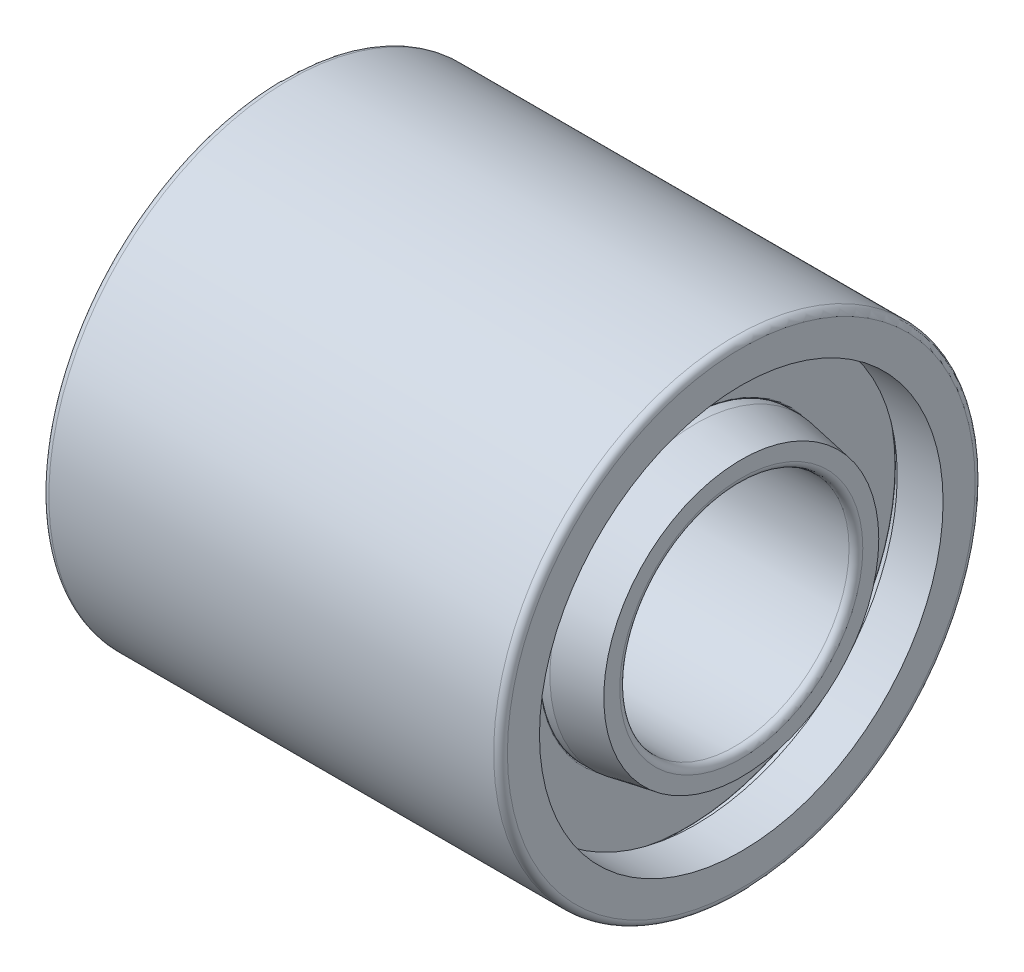
SolidWorks part; units mm, degrees
ref_plane "Plane1" through (0, 0, 0) normal (0, 0, 1) x (1, 0, 0)
ref_plane "Plane2" through (0, 0, 0) normal (0, 1, 0) x (1, 0, 0)
ref_plane "Plane3" through (0, 0, 0) normal (1, 0, 0) x (0, 0, -1)
sketch "Clipboard" plane through (0, 0, 0) normal (0, 0, 1) x (1, 0, 0)
  line L0 (-10, 0) -> (10, 0) construction
  line L1 (0, 0) -> (25.3745, -0.8861)
  line L2 (0, 0) -> (15.4906, 0.5409)
  line L3 (0, 0) -> (36.5877, -1.2777)
  line L4 (0, 0) -> (-22.3573, -0.3902)
  dimension "Race_OD" = 36.61
  dimension "Race_ID" = 25.39
sketch "OutRacSke" plane through (0, 0, 0) normal (0, 0, 1) x (1, 0, 0)
  line L0 (-16, 17.6038) -> (-20, 17.6038)
  line L1 (-20, 17.6038) -> (-20, 20.4)
  line L2 (-19.4, 21) -> (19.4, 21)
  line L3 (20, 20.4) -> (20, 17.6038)
  line L4 (20, 17.6038) -> (16, 17.6038)
  line L5 (16, 17.6038) -> (16, 18.305)
  line L6 (16, 18.305) -> (-16, 18.305)
  line L7 (-16, 18.305) -> (-16, 17.6038)
  line L8 (-90, 0) -> (90, 0) construction
  arc A0 (-20, 20.4) -> (-19.4, 21) centre (-19.4, 20.4) cw
  arc A1 (19.4, 21) -> (20, 20.4) centre (19.4, 20.4) cw
  dimension "Race_OD" = 36.61
  dimension "radius" = 0.6
  dimension "Width" = 40
  dimension "halfWidth" = 20
  dimension "groove_dp" = 0.7013
  dimension "Cyl_Len" = 32
revolve "OuterRace" add sketch "OutRacSke" angle 360 about L8 reverse direction yes
sketch "RolDetSke" plane through (0, 0, 0) normal (0, 0, 1) x (1, 0, 0)
  line L0 (-15.2, 18.1976) -> (-15.2, 15.5)
  line L1 (-15.2, 15.5) -> (15.2, 15.5)
  line L2 (15.2, 15.5) -> (15.2, 18.1976)
  line L3 (15.0876, 18.31) -> (-15.0876, 18.31)
  line L4 (-33.6, 15.5) -> (33.6, 15.5) construction
  arc A0 (15.2, 18.1976) -> (15.0876, 18.31) centre (15.0876, 18.1976) ccw
  arc A1 (-15.0876, 18.31) -> (-15.2, 18.1976) centre (-15.0876, 18.1976) ccw
  dimension "radius" = 0.1124
  dimension "Roller_diameter" = 5.62
  dimension "halfLength" = 15.2
revolve "RollerDetailed" [suppressed] add sketch "RolDetSke" angle 360 about L4 reverse direction yes
ref_axis "Axis1" through (-50, 0, 0) along (1, 0, 0)
sketch "RolSimSke" plane through (0, 101.6, 0) normal (0, 0, 1) x (1, 0, 0)
  line L0 (-15.2, -83.4024) -> (-15.2, -88.7976)
  line L1 (25.4, -101.6) -> (-25.4, -101.6) construction
  line L2 (15.2, -88.7976) -> (15.2, -83.4024)
  line L3 (15.0876, -83.29) -> (-15.0876, -83.29)
  line L5 (15.0876, -88.91) -> (-15.0876, -88.91)
  arc A0 (15.2, -83.4024) -> (15.0876, -83.29) centre (15.0876, -83.4024) ccw
  arc A1 (-15.0876, -83.29) -> (-15.2, -83.4024) centre (-15.0876, -83.4024) ccw
  arc A2 (15.2, -88.7976) -> (15.0876, -88.91) centre (15.0876, -88.7976) cw
  arc A3 (-15.0876, -88.91) -> (-15.2, -88.7976) centre (-15.0876, -88.7976) cw
  dimension "radius" = 0.1124
  dimension "D1" = 12.69
  dimension "Roller_diameter" = 5.62
  dimension "halfLength" = 15.2
revolve "RollersSimplified" add sketch "RolSimSke" angle 360 about L1
sketch "InsRacSke" plane through (0, 0, 0) normal (0, 0, 1) x (1, 0, 0)
  line L0 (-16, 12.695) -> (-20, 11.9938)
  line L1 (-20, 11.9938) -> (-20, 10.6)
  line L2 (-19.4, 10) -> (19.4, 10)
  line L3 (20, 10.6) -> (20, 11.9937)
  line L4 (20, 11.9937) -> (16, 12.695)
  line L5 (16, 12.695) -> (-16, 12.695)
  line L6 (-90, 0) -> (90, 0) construction
  line L7 (0, 0) -> (0, 177.8) construction
  arc A0 (-20, 10.6) -> (-19.4, 10) centre (-19.4, 10.6) ccw
  arc A1 (19.4, 10) -> (20, 10.6) centre (19.4, 10.6) ccw
  dimension "radius" = 0.6
  dimension "Race_ID" = 25.39
  dimension "Width" = 40
  dimension "halfWidth" = 20
  dimension "groove_dp" = 0.7013
  dimension "Cyl_Len" = 32
revolve "InnerRace" add sketch "InsRacSke" angle 360 about L6 reverse direction yes
pattern_circular "RollersDetailed" [suppressed] count 2 every 180 about axis through (-50, 0, 0) along (1, 0, 0)
sketch "CagSpiSke" plane through (0, 0, 0) normal (0, 0, 1) x (1, 0, 0)
  line L0 (18, 14.7975) -> (18, 16.2025)
  line L1 (18, 16.2025) -> (-18, 16.2025)
  line L2 (-18, 16.2025) -> (-18, 14.7975)
  line L3 (-18, 14.7975) -> (18, 14.7975)
  line L4 (-90, 0) -> (90, 0) construction
revolve "CageSpine" [suppressed] add sketch "CagSpiSke" angle 0.001 about L4
equation "\"CLdia@Clipboard\" =  ( \"Race_OD@Clipboard\" + \"Race_ID@Clipboard\" )  / 4"
equation "\"Race_OD@OutRacSke\" = \"Race_OD@Clipboard\""
equation "\"halfCylLen@OutRacSke\" = \"Cyl_Len@OutRacSke\" / 2"
equation "\"RolCLRad@RolDetSke\" = \"CLdia@Clipboard\""
equation "\"Roller_diameter@RolDetSke\" =  ( \"Race_OD@Clipboard\" - \"Race_ID@Clipboard\" )  / 2 + .01"
equation "\"Roller_diameter@RolSimSke\" =  ( \"Race_OD@Clipboard\" - \"Race_ID@Clipboard\" )  / 2 + .01"
equation "\"radius@RolDetSke\" = \"Roller_diameter@RolDetSke\" / 50"
equation "\"Length@RolDetSke\" = \"Cyl_Len@OutRacSke\" * .95"
equation "\"halfLength@RolDetSke\" = \"Length@RolDetSke\" / 2"
equation "\"thickness@CagSpiSke\"  = \"Roller_diameter@RolDetSke\" * .25"
equation "\"Cag_IR@CagSpiSke\" =  \"RolCLRad@RolDetSke\" * 2 - \"thickness@CagSpiSke\""
equation "\"Rol_Length@RolSimSke\" = \"Cyl_Len@InsRacSke\" * .95"
equation "\"halfLength@RolSimSke\" = \"Rol_Length@RolSimSke\" / 2"
equation "\"radius@RolSimSke\" = \"radius@RolDetSke\""
equation "\"D1@RolSimSke\" = \"CLdia@Clipboard\" -  ( \"Roller_diameter@RolSimSke\" / 2 ) "
equation "\"Max_count@Clipboard\" = int( 3.14159265 / atn(( \"Roller_diameter@RolDetSke\" / 2) / sqr( \"RolCLRad@RolDetSke\"  *  \"RolCLRad@RolDetSke\" - ( \"Roller_diameter@RolDetSke\" / 2) *  ( \"Roller_diameter@RolDetSke\" / 2))))"
equation "\"Max_count@Clipboard\" = ((sgn( \"Max_count@Clipboard\" - \"Count@Clipboard\" )-1)*( \"Max_count@Clipboard\" - \"Count@Clipboard\" ))/-2+ \"Count@Clipboard\""
equation "\"Count@RollersDetailed\" = int( \"Show_count@Clipboard\" ) "
equation "\"Count@RollersDetailed\" = ((sgn( \"Count@RollersDetailed\" - \"Max_count@Clipboard\" )-1)*( \"Count@RollersDetailed\" - \"Max_count@Clipboard\" ))/-2+ \"Max_count@Clipboard\""
equation "\"Count@RollersDetailed\" = ((sgn( \"Count@RollersDetailed\" - \"Min_count@Clipboard\" )+1)*( \"Count@RollersDetailed\" - \"Min_count@Clipboard\"))/2 +\"Min_count@Clipboard\""
equation "\"Angle@RollersDetailed\" = 360.0 / \"Max_count@Clipboard\""
equation "\"radius@InsRacSke\" = \"radius@OutRacSke\""
equation "\"groove_dp@InsRacSke\" = \"groove_dp@OutRacSke\""
equation "\"Width@InsRacSke\" = \"Width@OutRacSke\""
equation "\"halfWidth@OutRacSke\" = \"Width@OutRacSke\" / 2"
equation "\"halfWidth@InsRacSke\" = \"Width@InsRacSke\" / 2"
equation "\"Race_ID@InsRacSke\" = \"Race_ID@Clipboard\""
equation "\"Cyl_Len@InsRacSke\" = \"Cyl_Len@OutRacSke\""
equation "\"Angle@CageSpine\" =  \"Angle@RollersDetailed\" * ( \"Count@RollersDetailed\" -1 + int( \"Count@RollersDetailed\" / \"Max_count@Clipboard\" ) )  + 0.001 -  int( \"Count@RollersDetailed\" / \"Max_count@Clipboard\" ) * 0.001"
equation "\"Angle@CageSpine\" =  \"Angle@CageSpine\" * int( \"Min_count@Clipboard\" / 2) + int(1 / \"Min_count@Clipboard\")  * 0.001"
equation "\"width@CagSpiSke\" =   ( \"Width@InsRacSke\" + \"Cyl_Len@InsRacSke\" )  / 2"
equation "\"halfwidth@CagSpiSke\" = \"width@CagSpiSke\" / 2"
